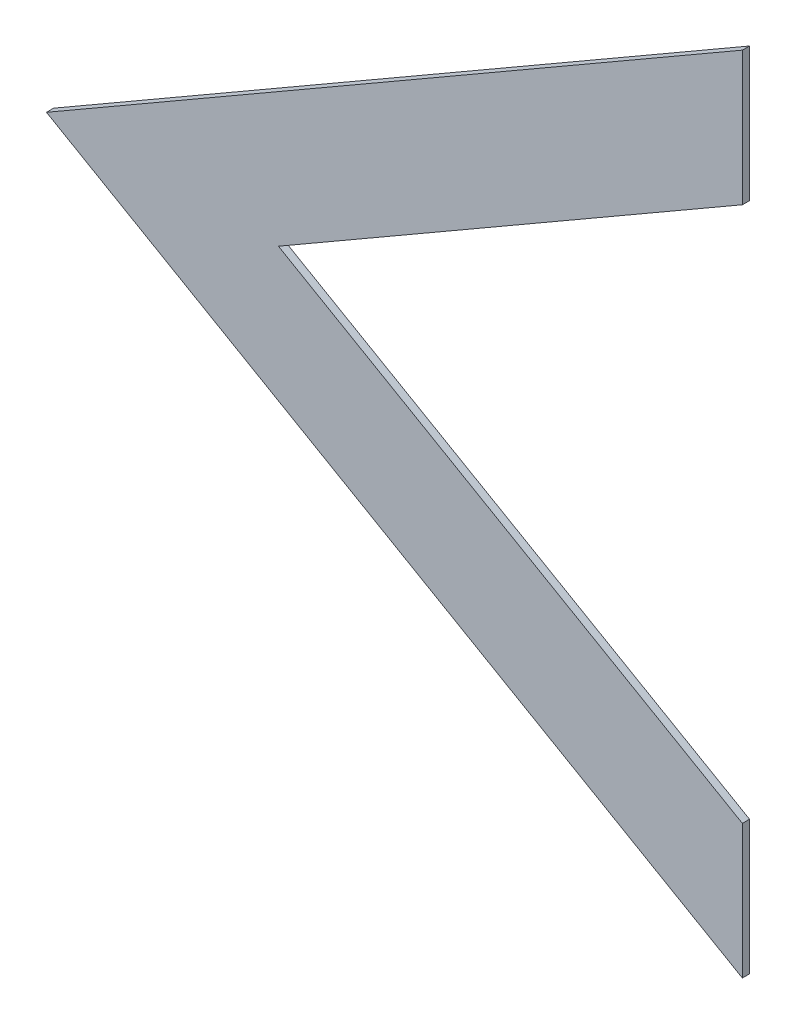
SolidWorks part; units mm, degrees
ref_plane "Front Plane" through (0, 0, 0) normal (0, 0, 1) x (1, 0, 0)
ref_plane "Top Plane" through (0, 0, 0) normal (0, 1, 0) x (1, 0, 0)
ref_plane "Right Plane" through (0, 0, 0) normal (1, 0, 0) x (0, 0, -1)
sketch "Sketch1" plane through (0, 0, 0) normal (0, 0, 1) x (1, 0, 0)
  line L6 (43.3775, 53.25) -> (-5.1199, 25.25)
  line L7 (-5.1199, 25.25) -> (43.3775, -2.75)
  line L8 (43.3775, -2.75) -> (43.3775, 6.5833)
  line L9 (43.3775, 6.5833) -> (11.0459, 25.25)
  line L10 (11.0459, 25.25) -> (43.3775, 43.9167)
  line L11 (43.3775, 43.9167) -> (43.3775, 53.25)
  line L12 (43.3775, 53.25) -> (-5.1199, 25.25)
  line L13 (-5.1199, 25.25) -> (43.3775, -2.75)
  line L14 (43.3775, -2.75) -> (43.3775, 6.5833)
  line L15 (43.3775, 6.5833) -> (11.0459, 25.25)
  line L16 (11.0459, 25.25) -> (43.3775, 43.9167)
  line L17 (43.3775, 43.9167) -> (43.3775, 53.25)
  dimension "D1" = 0
extrude "Boss-Extrude1" add sketch "Sketch1" against normal up to surface (0.5 mm away)
